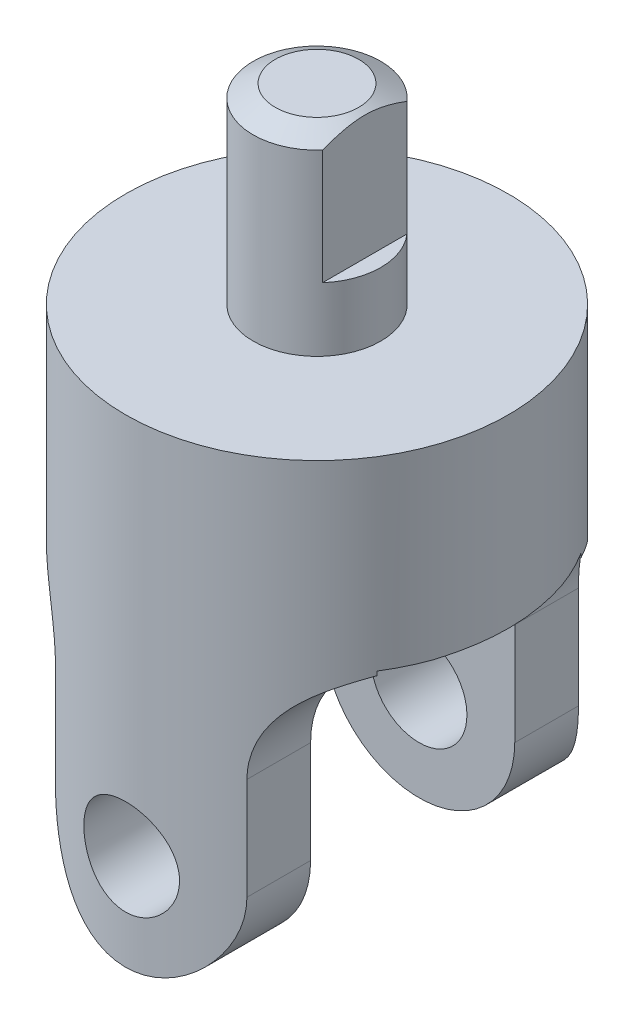
SolidWorks part; units mm, degrees
note: '?' marks a value the reader was unsure of.
ref_plane "Front" through (0, 0, 0) normal (0, 0, 1) x (1, 0, 0)
ref_plane "Top" through (0, 0, 0) normal (0, 1, 0) x (-1, 0, 0)
ref_plane "Right" through (0, 0, 0) normal (1, 0, 0) x (0, 0, -1)
sketch "Sketch1" plane through (0, 0, 0) normal (0, 1, 0) x (-1, 0, 0)
  circle A0 centre (0, 0) radius 19.05
  dimension "D1" = 38.1
extrude "Base-Extrude" add sketch "Sketch1" along normal blind 47.625
sketch "Sketch2" plane through (0, 0, 0) normal (0, 0, 1) x (1, 0, 0)
  line L0 (0, 0) -> (0, 23.7435) construction
  line L1 (9.525, 9.525) -> (9.525, 19.685)
  line L2 (-9.525, 9.525) -> (-9.525, 19.685)
  line L3 (19.05, 29.21) -> (19.05, -1.3662)
  line L4 (19.05, -1.3662) -> (-19.05, -1.3662)
  line L5 (-19.05, -1.3662) -> (-19.05, 29.21)
  line L6 (19.05, 0) -> (-19.05, 0) construction
  arc A0 (-9.525, 9.525) -> (9.525, 9.525) centre (0, 9.525) ccw
  arc A1 (9.525, 19.685) -> (19.05, 29.21) centre (19.05, 19.685) cw
  arc A2 (-9.525, 19.685) -> (-19.05, 29.21) centre (-19.05, 19.685) ccw
  dimension "D3" = 9.525
  dimension "D1" = 38.1
  dimension "D2" = 19.05
  dimension "D4" = 29.21
extrude "Cut-Extrude1" cut sketch "Sketch2" against normal through all and the other way through all
sketch "Sketch8" plane through (0, 0, 0) normal (1, 0, 0) x (0, 0, -1)
  line L0 (-10.16, -7.4553) -> (10.16, -7.4553)
  line L1 (-10.16, -7.4553) -> (-10.16, 29.1452)
  line L2 (10.16, 29.1452) -> (-10.16, 29.1452)
  line L3 (10.16, 29.1452) -> (10.16, -7.4553)
  point P4 (0, 0)
  dimension "D1" = 10.16
  dimension "D2" = 20.32
extrude "Cut-Extrude5" cut sketch "Sketch8" against normal through all and the other way blind 47.625
sketch "Sketch11" plane through (0, 0, 0) normal (0, 0, 1) x (1, 0, 0)
  circle A0 centre (0, 9.525) radius 4.7625
  dimension "D1" = 9.525
extrude "Cut-Extrude6" cut sketch "Sketch11" against normal through all and the other way through all
sketch "Sketch12" plane through (0, 47.625, 0) normal (0, 1, 0) x (-1, 0, 0)
  circle A0 centre (0, 0) radius 6.35
  dimension "D1" = 12.7
extrude "Boss-Extrude1" add sketch "Sketch12" along normal blind 19.05
chamfer "Chamfer3" distance 1.27 angle 60 1 edges at (0, 66.675, 6.35) first distance on face at (0, 66.675, 6.35)
ref_axis "Axis1" through (0, 97.625, 0) along (0, -1, 0)?
sketch "Sketch13" plane through (0, 66.675, 0) normal (0, 1, 0) x (-1, 0, 0)
  line L0 (-4.7625, 4.2001) -> (-4.7625, -4.2001)
  circle A0 centre (0, 0) radius 6.35 construction
  arc A1 (-4.7625, 4.2001) -> (-4.7625, -4.2001) centre (0, 0) ccw
  dimension "D1" = 1.5875
extrude "Cut-Extrude7" cut sketch "Sketch13" against normal blind 12.7
